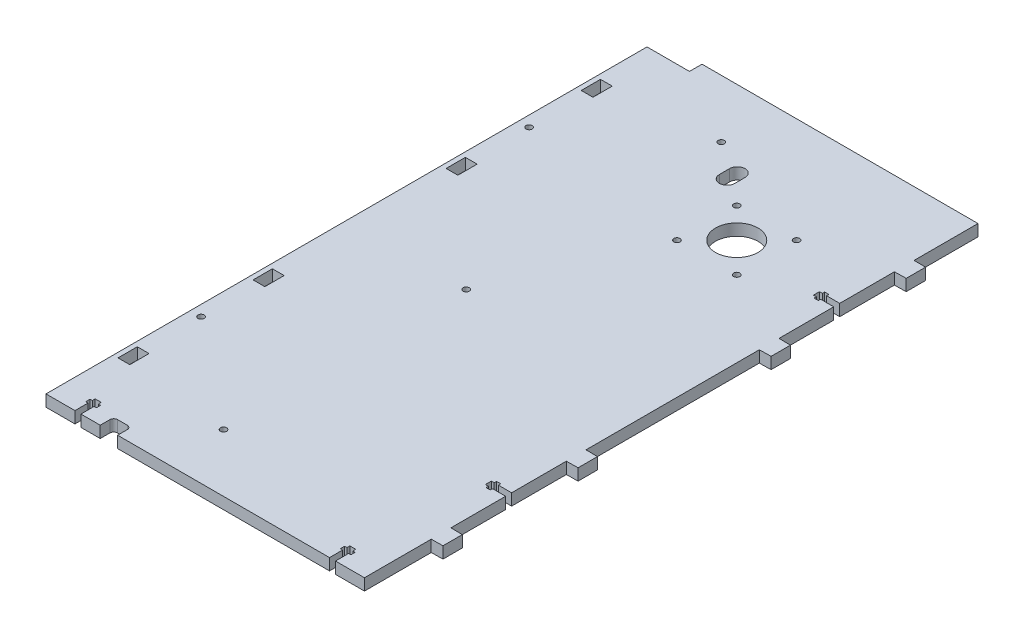
SolidWorks part; units mm, degrees
material "Клен"
ref_plane "Front" through (0, 0, 0) normal (0, 0, 1) x (1, 0, 0)
ref_plane "Top" through (0, 0, 0) normal (0, 1, 0) x (1, 0, 0)
ref_plane "Right" through (0, 0, 0) normal (1, 0, 0) x (0, 0, -1)
sketch "Эскиз1" plane through (0, 0, 6) normal (0, 1, 0) x (1, 0, 0)
  line L0 (830.1555, 858.9465) -> (830.1555, 507.3335) construction
  line L1 (746.0135, 673.4222) -> (945.6578, 673.4222) construction
  line L2 (746.0135, 805.6234) -> (945.6578, 805.6234) construction
  line L3 (746.0135, 547.7211) -> (945.6578, 547.7211) construction
  line L4 (883.1555, 853.0128) -> (883.1555, 710.7402) construction
  line L9 (920.8397, 790.6234) -> (837.8362, 790.6234) construction
  line L10 (848.1555, 798.0451) -> (848.1555, 726.8571) construction
  line L11 (844.1555, 795.9063) -> (844.1555, 790.6234)
  line L12 (852.1555, 790.6234) -> (852.1555, 795.9063)
  line L16 (776.7555, 552.5234) -> (776.7555, 562.5234)
  line L17 (770.6555, 562.5234) -> (770.6555, 552.5234)
  line L18 (770.6555, 552.5234) -> (776.7555, 552.5234)
  line L19 (776.7555, 562.5234) -> (770.6555, 562.5234)
  line L20 (770.6555, 622.5234) -> (776.7555, 622.5234)
  line L21 (776.7555, 622.5234) -> (776.7555, 632.5234)
  line L22 (776.7555, 632.5234) -> (770.6555, 632.5234)
  line L23 (770.6555, 632.5234) -> (770.6555, 622.5234)
  line L24 (776.7555, 722.5234) -> (776.7555, 732.5234)
  line L25 (770.6555, 722.5234) -> (776.7555, 722.5234)
  line L26 (770.6555, 732.5234) -> (770.6555, 722.5234)
  line L27 (776.7555, 732.5234) -> (770.6555, 732.5234)
  line L28 (770.6555, 792.5234) -> (776.7555, 792.5234)
  line L29 (776.7555, 792.5234) -> (776.7555, 802.5234)
  line L30 (776.7555, 802.5234) -> (770.6555, 802.5234)
  line L31 (770.6555, 802.5234) -> (770.6555, 792.5234)
  line L32 (833.1555, 858.9465) -> (833.1555, 507.3335) construction
  line L33 (933.1555, 858.9465) -> (933.1555, 507.3335) construction
  line L34 (933.1555, 517.7211) -> (933.1555, 552.3234)
  line L35 (933.1555, 593.9734) -> (933.1555, 622.3234)
  line L36 (933.1555, 622.3234) -> (939.1555, 622.4234)
  line L37 (924.1555, 589.6734) -> (924.1555, 590.8734)
  line L38 (939.1555, 722.4234) -> (939.1555, 732.4234)
  line L39 (939.1555, 562.4234) -> (933.1555, 562.5234)
  line L40 (924.1555, 765.1734) -> (926.3555, 765.1734)
  line L41 (933.1555, 562.5234) -> (933.1555, 590.8734)
  line L42 (926.3555, 589.6734) -> (924.1555, 589.6734)
  line L43 (922.6555, 760.8734) -> (922.6555, 763.9734)
  line L44 (926.3555, 759.6734) -> (924.1555, 759.6734)
  line L45 (933.1555, 763.9734) -> (933.1555, 792.3234)
  line L46 (926.3555, 595.1734) -> (926.3555, 593.9734)
  line L47 (926.3555, 760.8734) -> (926.3555, 759.6734)
  line L48 (939.1555, 622.4234) -> (939.1555, 632.4234)
  line L49 (939.1555, 732.4234) -> (933.1555, 732.5234)
  line L50 (926.3555, 763.9734) -> (933.1555, 763.9734)
  line L51 (926.3555, 593.9734) -> (933.1555, 593.9734)
  line L52 (924.1555, 760.8734) -> (922.6555, 760.8734)
  line L53 (933.1555, 590.8734) -> (926.3555, 590.8734)
  line L54 (933.1555, 632.5234) -> (933.1555, 722.3234)
  line L55 (924.1555, 763.9734) -> (924.1555, 765.1734)
  line L56 (933.1555, 802.5234) -> (933.1555, 835.6234)
  line L57 (924.1555, 590.8734) -> (922.6555, 590.8734)
  line L58 (924.1555, 595.1734) -> (926.3555, 595.1734)
  line L59 (933.1555, 792.3234) -> (939.1555, 792.4234)
  line L60 (933.1555, 760.8734) -> (926.3555, 760.8734)
  line L61 (922.6555, 763.9734) -> (924.1555, 763.9734)
  line L124 (805.2555, 522.7211) -> (805.2555, 517.7211)
  line L125 (805.2555, 517.7211) -> (833.1555, 517.7211)
  line L167 (833.1555, 835.6234) -> (790.1555, 835.6234)
  line L168 (790.1555, 835.6234) -> (790.1555, 829.1234)
  line L169 (790.1555, 829.1234) -> (768.1555, 829.1234)
  line L170 (768.1555, 829.1234) -> (768.1555, 517.7211)
  line L171 (768.1555, 517.7211) -> (783.1555, 517.7211)
  line L172 (783.1555, 517.7211) -> (783.1555, 524.5211)
  line L173 (783.1555, 524.5211) -> (781.9555, 524.5211)
  line L174 (781.9555, 524.5211) -> (781.9555, 526.7211)
  line L175 (781.9555, 526.7211) -> (783.1555, 526.7211)
  line L176 (783.1555, 526.7211) -> (783.1555, 528.2211)
  line L177 (783.1555, 528.2211) -> (786.2555, 528.2211)
  line L178 (786.2555, 528.2211) -> (786.2555, 526.7211)
  line L179 (786.2555, 526.7211) -> (787.4555, 526.7211)
  line L180 (787.4555, 526.7211) -> (787.4555, 524.5211)
  line L181 (787.4555, 524.5211) -> (786.2555, 524.5211)
  line L182 (786.2555, 524.5211) -> (786.2555, 517.7211)
  line L183 (786.2555, 517.7211) -> (796.2555, 517.7211)
  line L184 (796.2555, 517.7211) -> (796.2555, 522.7211)
  line L185 (798.2555, 524.7211) -> (803.2555, 524.7211)
  line L186 (926.3555, 590.8734) -> (926.3555, 589.6734)
  line L187 (939.1555, 632.4234) -> (933.1555, 632.5234)
  line L188 (933.1555, 552.3234) -> (939.1555, 552.4234)
  line L189 (922.6555, 590.8734) -> (922.6555, 593.9734)
  line L190 (933.1555, 722.3234) -> (939.1555, 722.4234)
  line L191 (933.1555, 732.5234) -> (933.1555, 760.8734)
  line L192 (924.1555, 593.9734) -> (924.1555, 595.1734)
  line L193 (924.1555, 759.6734) -> (924.1555, 760.8734)
  line L194 (926.3555, 765.1734) -> (926.3555, 763.9734)
  line L195 (939.1555, 802.4234) -> (933.1555, 802.5234)
  line L196 (939.1555, 552.4234) -> (939.1555, 562.4234)
  line L197 (922.6555, 593.9734) -> (924.1555, 593.9734)
  line L198 (939.1555, 792.4234) -> (939.1555, 802.4234)
  line L199 (833.1555, 835.6234) -> (933.1555, 835.6234)
  line L200 (933.1555, 517.7211) -> (918.1555, 517.7211)
  line L201 (915.0555, 517.7211) -> (915.0555, 524.5211)
  line L202 (913.8555, 526.7211) -> (915.0555, 526.7211)
  line L203 (919.3555, 524.5211) -> (918.1555, 524.5211)
  line L204 (915.0555, 524.5211) -> (913.8555, 524.5211)
  line L205 (918.1555, 526.7211) -> (919.3555, 526.7211)
  line L206 (918.1555, 524.5211) -> (918.1555, 517.7211)
  line L207 (915.0555, 526.7211) -> (915.0555, 528.2211)
  line L208 (913.8555, 524.5211) -> (913.8555, 526.7211)
  line L209 (918.1555, 528.2211) -> (918.1555, 526.7211)
  line L210 (915.0555, 528.2211) -> (918.1555, 528.2211)
  line L211 (919.3555, 526.7211) -> (919.3555, 524.5211)
  line L212 (915.0555, 517.7211) -> (833.1555, 517.7211)
  circle A0 centre (830.1555, 805.6234) radius 1.6
  circle A1 centre (830.1555, 673.4222) radius 1.6
  circle A2 centre (830.1555, 547.7211) radius 1.6
  circle A3 centre (862.6555, 781.1234) radius 1.6
  arc A4 (805.2555, 522.7211) -> (803.2555, 524.7211) centre (803.2555, 522.7211) ccw
  arc A5 (798.2555, 524.7211) -> (796.2555, 522.7211) centre (798.2555, 522.7211) ccw
  circle A6 centre (773.7055, 592.5234) radius 1.6
  circle A7 centre (773.7055, 762.5234) radius 1.6
  circle A8 centre (862.6555, 750.1234) radius 1.6
  circle A9 centre (878.1555, 765.6234) radius 11
  circle A10 centre (893.6555, 750.1234) radius 1.6
  circle A11 centre (893.6555, 781.1234) radius 1.6
  arc A16 (852.1555, 795.9063) -> (844.1555, 795.9063) centre (848.1555, 795.9063) ccw
  arc A17 (844.1555, 790.6234) -> (852.1555, 790.6234) centre (848.1555, 790.6234) ccw
  dimension "D7" = 3.2
  dimension "D8" = 3.2
  dimension "D9" = 3.2
  dimension "D11" = 15.5
  dimension "D12" = 31
  dimension "D13" = 31
  dimension "D14" = 31
  dimension "D15" = 70
  dimension "D17" = 25
  dimension "D18" = 30
  dimension "D2" = 100
  dimension "D3" = 15
  dimension "D4" = 30
  dimension "D1" = 3
  dimension "D5" = 30
  dimension "D6" = 162.2012
  dimension "D10" = 50
  dimension "D16" = 45
extrude "Бобышка-Вытянуть1" add sketch "Эскиз1" against normal blind 6
